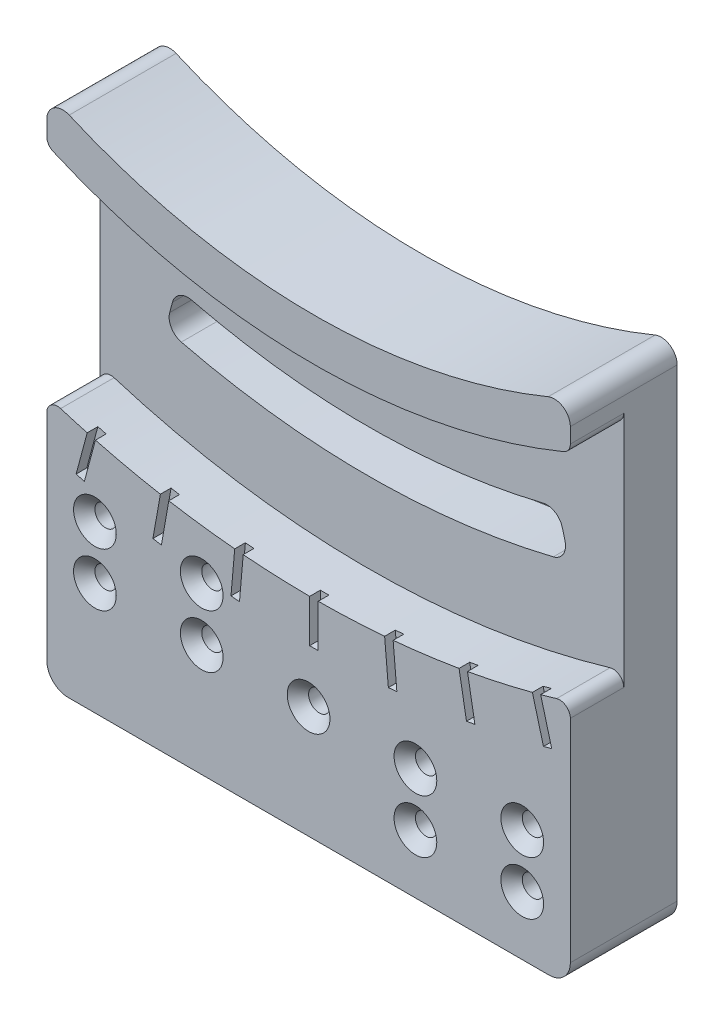
SolidWorks part; units mm, degrees
ref_plane "Front Plane" through (0, 0, 0) normal (0, 0, 1) x (1, 0, 0)
ref_plane "Top Plane" through (0, 0, 0) normal (0, 1, 0) x (1, 0, 0)
ref_plane "Right Plane" through (0, 0, 0) normal (1, 0, 0) x (0, 0, -1)
sketch "Sketch1" plane through (0, 0, 0) normal (0, 0, 1) x (1, 0, 0)
  line L0 (16.5, 10.5204) -> (16.5, 2.5204) construction
  line L1 (-20.5, -2.4796) -> (3.5, -2.4796)
  line L2 (-20.5, -2.4796) -> (-20.5, -10.4796)
  line L3 (-20.5, -10.4796) -> (3.5, -10.4796)
  line L4 (3.5, -2.4796) -> (3.5, -10.4796)
  line L5 (4.5, 10.5204) -> (28.5, 10.5204)
  line L6 (4.5, 10.5204) -> (4.5, 2.5204)
  line L7 (4.5, 2.5204) -> (28.5, 2.5204)
  line L8 (28.5, 10.5204) -> (28.5, 2.5204)
  line L9 (16.5, 6.5204) -> (4.5, 6.5204) construction
  line L10 (-8.5, -10.4796) -> (-8.5, -2.4796) construction
  line L11 (-8.5, -6.4796) -> (3.5, -6.4796) construction
  line L12 (-20.5, 0.0204) -> (28.5, 0.0204) construction
  line L13 (-20.5, -10.4796) -> (28.5, -10.4796)
  line L14 (-20.5, -10.4796) -> (-20.5, 10.5204)
  line L15 (-20.5, 10.5204) -> (28.5, 10.5204)
  line L16 (28.5, -10.4796) -> (28.5, 10.5204)
  line L17 (-20.5, 10.5204) -> (28.5, -10.4796) construction
  line L18 (-20.5, 5.0204) -> (4.5, 5.0204) construction
  line L19 (3.5, -4.9796) -> (28.5, -4.9796) construction
  line L20 (24, 0.0204) -> (24, -4.9796) construction
  circle A0 centre (10.5, 8.5204) radius 1
  circle A1 centre (7.5, 6.5204) radius 1
  circle A2 centre (10.5, 4.5204) radius 1
  circle A3 centre (22.5, 4.5204) radius 1
  circle A4 centre (25.5, 6.5204) radius 1
  circle A5 centre (22.5, 8.5204) radius 1
  circle A6 centre (0.5, -6.4796) radius 1
  circle A7 centre (-14.5, -4.4796) radius 1
  circle A8 centre (-2.5, -8.4796) radius 1
  circle A9 centre (-2.5, -4.4796) radius 1
  circle A10 centre (-17.5, -6.4796) radius 1
  circle A11 centre (-14.5, -8.4796) radius 1
  circle A12 centre (4, 0.0204) radius 1
  circle A13 centre (14, -4.9796) radius 1
  circle A14 centre (24, -4.9796) radius 1
  circle A15 centre (-6, 5.0204) radius 1
  circle A16 centre (-16, 5.0204) radius 1
  circle A17 centre (-6, 0.0204) radius 1
  circle A18 centre (-16, 0.0204) radius 1
  circle A19 centre (14, 0.0204) radius 1
  circle A20 centre (24, 0.0204) radius 1
  dimension "D7" = 2
  dimension "D8" = 9
  dimension "D15" = 2
  dimension "D16" = 2
  dimension "D17" = 2
  dimension "D18" = 2
  dimension "D19" = 2
  dimension "D20" = 2
  dimension "D21" = 2
  dimension "D22" = 2
  dimension "D23" = 2
  dimension "D24" = 2
  dimension "D25" = 2
  dimension "D26" = 2
  dimension "D27" = 2
  dimension "D1" = 8
  dimension "D2" = 8
  dimension "D3" = 1
  dimension "D4" = 24
  dimension "D5" = 24
  dimension "D6" = 5
  dimension "D9" = 6
  dimension "D10" = 2
  dimension "D11" = 9
  dimension "D12" = 6
  dimension "D13" = 2
  dimension "D14" = 12
  dimension "D28" = 24.5
  dimension "D29" = 20
  dimension "D30" = 10
  dimension "D31" = 10
  dimension "D32" = 10
  dimension "D33" = 20
  dimension "D34" = 10
extrude "Boss-Extrude4" add sketch "Sketch1" along normal blind 10 contours L13 L16 L7 L6 L15 L14 L1 L4 A20 A19 A18 A17 A16 A15 A14 A13 A12 | L3 L4 L1 L2 | L8 L7 L6 L5 region at (-19.9669, 4.0204, 0)
chamfer "Chamfer2" distance 1 angle 45 9 edges at (-15, 0.0204, 10) (-15, 5.0204, 10) (-5, 5.0204, 10) (-5, 0.0204, 10) (5, 0.0204, 10) (25, 0.0204, 10) (15, 0.0204, 10) (15, -4.9796, 10) (25, -4.9796, 10)
fillet "Fillet2" radius 2 2 edges at (-20.5, -10.4796, 5) (28.5, -10.4796, 5)
sketch "Sketch2" plane through (0, 10.5204, 0) normal (0, 1, 0) x (1, 0, 0)
  line L4 (28.5, 0) -> (-20.5, 0)
  line L5 (-20.5, 0) -> (-20.5, -10)
  line L6 (-20.5, -10) -> (28.5, -10)
  line L7 (28.5, -10) -> (28.5, 0)
  line L8 (28.5, 0) -> (-20.5, 0)
  line L9 (-20.5, 0) -> (-20.5, -10)
  line L10 (-20.5, -10) -> (28.5, -10)
  line L11 (28.5, -10) -> (28.5, 0)
  dimension "D1" = 0
extrude "Boss-Extrude5" add sketch "Sketch2" along normal blind 30
sketch "Sketch4" plane through (0, 0, 10) normal (0, 0, 1) x (1, 0, 0)
  line L0 (4.5, 89.5204) -> (4.5, 9.0204) construction
  line L2 (-20.5, -8.4796) -> (-20.5, 40.5204) construction
  line L3 (4.5, 89.5204) -> (-57.1666, 37.776) construction
  line L4 (4.5, 89.5204) -> (69.1618, 41.5715) construction
  line L5 (4.5, 89.5204) -> (18.4786, 10.2433) construction
  line L6 (4.5, 89.5204) -> (-9.4787, 10.2433) construction
  line L7 (-18.5, -10.4796) -> (26.5, -10.4796) construction
  line L8 (4.5, 89.5204) -> (25.3349, 11.7633) construction
  line L9 (4.5, 89.5204) -> (45.7285, 30.6399) construction
  line L10 (44.0767, 32.9989) -> (45.7285, 30.6399)
  line L11 (4.5, 89.5204) -> (-41.6729, 23.5786) construction
  line L12 (-35.0768, 32.9989) -> (-37.3711, 29.7223)
  line L13 (22.3585, 22.8715) -> (23.3937, 19.0078)
  line L14 (4.5, 89.5204) -> (-16.335, 11.7633) construction
  line L15 (-13.3586, 22.8715) -> (-14.3938, 19.0078)
  line L16 (-1.769, 13.2766) -> (-2.5659, 13.3463)
  line L17 (4.9, 13.0204) -> (4.1, 13.0204)
  line L18 (4.9, 13.0204) -> (4.9, 5.0204)
  line L19 (4.9, 5.0204) -> (4.1, 5.0204)
  line L20 (4.1, 13.0204) -> (4.1, 5.0204)
  line L21 (4.5, 5.0204) -> (4.5, 13.0204) construction
  line L22 (4.9, 9.0204) -> (4.1, 9.0204) construction
  line L23 (-1.769, 13.2766) -> (-2.4662, 5.3071)
  line L24 (-2.4662, 5.3071) -> (-3.2632, 5.3768)
  line L25 (-2.5659, 13.3463) -> (-3.2632, 5.3768)
  line L26 (-2.8647, 5.3419) -> (-2.1675, 13.3115) construction
  line L27 (-2.1176, 9.2918) -> (-2.9146, 9.3616) construction
  line L28 (-8.3902, 14.1131) -> (-9.1781, 14.252)
  line L29 (-8.3902, 14.1131) -> (-9.7794, 6.2347)
  line L30 (-9.7794, 6.2347) -> (-10.5672, 6.3736)
  line L31 (-9.1781, 14.252) -> (-10.5672, 6.3736)
  line L32 (-10.1733, 6.3041) -> (-8.7841, 14.1826) construction
  line L33 (-9.0848, 10.1739) -> (-9.8726, 10.3128) construction
  line L34 (-14.9133, 15.5235) -> (-15.6861, 15.7306)
  line L35 (-14.9133, 15.5235) -> (-16.9839, 7.7961)
  line L36 (-16.9839, 7.7961) -> (-17.7566, 8.0032)
  line L37 (-15.6861, 15.7306) -> (-17.7566, 8.0032)
  line L38 (-17.3703, 7.8996) -> (-15.2997, 15.627) construction
  line L39 (-15.9486, 11.6598) -> (-16.7213, 11.8669) construction
  line L40 (11.5658, 13.3463) -> (10.7689, 13.2766)
  line L41 (11.5658, 13.3463) -> (12.2631, 5.3768)
  line L42 (12.2631, 5.3768) -> (11.4661, 5.3071)
  line L43 (10.7689, 13.2766) -> (11.4661, 5.3071)
  line L44 (11.8646, 5.3419) -> (11.1674, 13.3115) construction
  line L45 (11.9145, 9.3616) -> (11.1175, 9.2918) construction
  line L46 (18.178, 14.252) -> (17.3901, 14.1131)
  line L47 (18.178, 14.252) -> (19.5671, 6.3736)
  line L48 (19.5671, 6.3736) -> (18.7793, 6.2347)
  line L49 (17.3901, 14.1131) -> (18.7793, 6.2347)
  line L50 (19.1732, 6.3041) -> (17.784, 14.1826) construction
  line L51 (18.8726, 10.3128) -> (18.0847, 10.1739) construction
  line L52 (24.686, 15.7306) -> (23.9132, 15.5235)
  line L53 (24.686, 15.7306) -> (26.7565, 8.0032)
  line L54 (26.7565, 8.0032) -> (25.9838, 7.7961)
  line L55 (23.9132, 15.5235) -> (25.9838, 7.7961)
  line L56 (26.3702, 7.8996) -> (24.2996, 15.627) construction
  line L57 (25.7213, 11.8669) -> (24.9485, 11.6598) construction
  circle A0 centre (4.5, 89.5204) radius 61.5
  circle A1 centre (4.5, 89.5204) radius 80.5
  circle A2 centre (4.5, 89.5204) radius 73
  circle A3 centre (4.5, 89.5204) radius 69
  circle A4 centre (4.5, 89.5204) radius 57.5
  point P60 (4.5, 89.5204)
  point P85 (4.5, 89.5204)
  line M10 (-20.5, 40.5204) -> (-20.5, -8.4796)
  line M14 (28.5, -8.4796) -> (28.5, 40.5204)
  line M15 (28.5, 40.5204) -> (-20.5, 40.5204)
  dimension "D1" = 80.5
  dimension "D2" = 61.5
  dimension "D8" = 73
  dimension "D9" = 69
  dimension "D18" = 115
  dimension "D3" = 100
  dimension "D4" = 50
  dimension "D5" = 25
  dimension "D6" = 10
  dimension "D7" = 10
  dimension "D10" = 35
  dimension "D11" = 35
  dimension "D12" = 5
  dimension "D13" = 5
  dimension "D14" = 0.8
  dimension "D15" = 8
  dimension "D16" = 4
  dimension "D17" = 4
extrude "Cut-Extrude1" cut sketch "Sketch4" against normal blind 73 contours A3 L15 A2 L13 | A4 M10 M14 M15 region at (4.5, 19.3101, 10) region at (4.2751, 36.9694, 10)
extrude "Cut-Extrude2" cut sketch "Sketch4<3>" against normal blind 5 contours A3 A0 M10 M14 | A3 L13 A2 M14 | A2 A1 L37 L34 L35 L31 L28 L29 L25 L16 L23 L20 L17 L18 L43 L40 L41 L49 L46 L47 L55 L52 L53 M10 M14 | A3 A2 L15 M10 | L55 A1 L53 L52 | L49 A1 L47 L46 | L43 A1 L41 L40 | L20 A1 L18 L17 | L37 A1 L35 L34 | L25 A1 L23 L16 | L31 A1 L29 L28 region at (3.9736, 25.8781, 10) region at (-17.1988, 22.0038, 10) region at (3.9485, 14.2405, 10) region at (25.6923, 21.8443, 10) region at (-15.8173, 13.6954, 10) region at (24.8172, 13.6954, 10) region at (-9.1314, 12.2131, 10) region at (18.1313, 12.2131, 10) region at (-2.3418, 11.3193, 10) region at (11.3417, 11.3193, 10) region at (4.5, 11.0205, 10)
sketch "Sketch4<3>" plane through (0, 0, 10) normal (0, 0, 1) x (1, 0, 0) same geometry as "Sketch4"
extrude "Cut-Extrude3" cut sketch "Sketch4<4>" against normal blind 1 contours A1 L43 L42 L41 | A1 L37 L36 L35 | L37 A1 L35 L34 | L53 L54 L55 L52 | L47 L48 L49 L46 | L18 L19 L20 L17 | L41 L42 L43 L40 | L23 L24 L25 L16 | L29 L30 L31 L28 region at (11.6903, 7.3345, 10) region at (-15.8173, 13.6954, 10) region at (-16.8526, 9.8317, 10)
sketch "Sketch4<4>" plane through (0, 0, 10) normal (0, 0, 1) x (1, 0, 0) same geometry as "Sketch4"
fillet "Fillet4" radius 1.5 4 edges at (-14.3938, 19.0078, 2.5) (-13.3586, 22.8715, 2.5) (22.3585, 22.8715, 2.5) (23.3937, 19.0078, 2.5)
fillet "Fillet6" radius 1.5 2 edges at (-20.5, 37.7396, 5) (28.5, 37.2686, 5)
fillet "Fillet7" radius 1 4 edges at (28.5, 12.6813, 7.5) (-20.5, 13.0008, 7.5) (-20.5, 33.331, 7.5) (28.5, 32.8966, 7.5)
